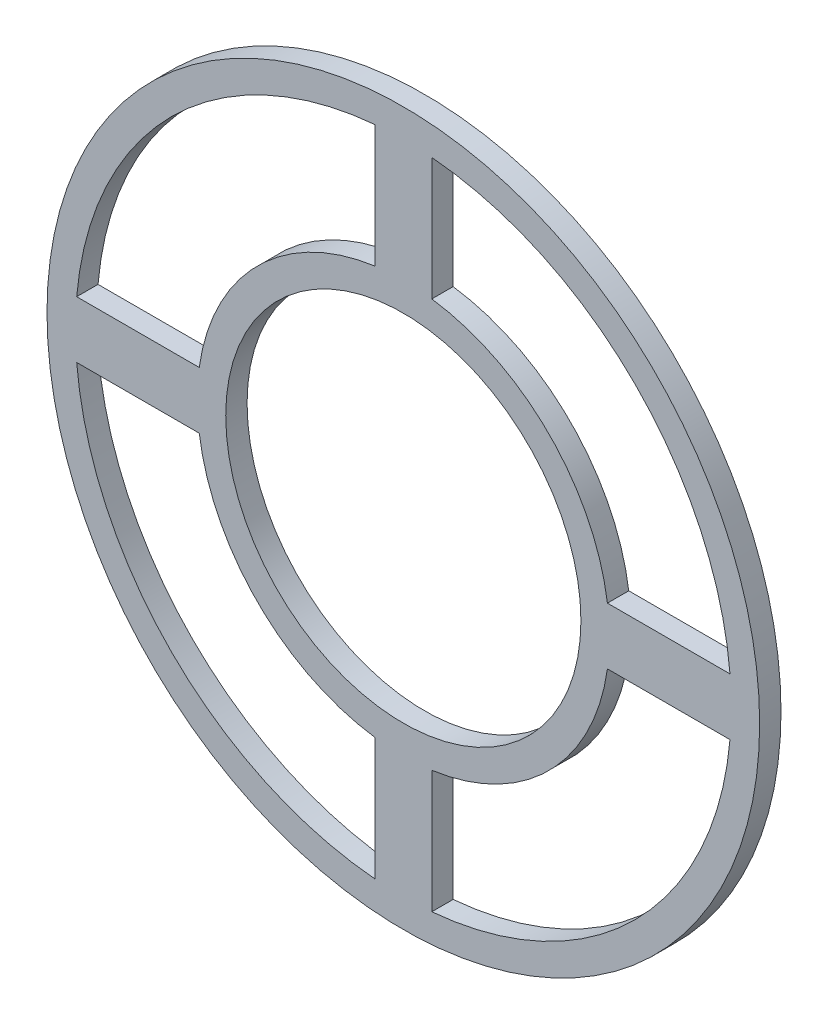
SolidWorks part; units mm, degrees
ref_plane "Front Plane" through (0, 0, 0) normal (0, 0, 1) x (1, 0, 0)
ref_plane "Top Plane" through (0, 0, 0) normal (0, 1, 0) x (1, 0, 0)
ref_plane "Right Plane" through (0, 0, 0) normal (1, 0, 0) x (0, 0, -1)
sketch "Sketch1" plane through (0, 0, 0) normal (0, 0, 1) x (1, 0, 0)
  line L0 (-6.35, 45.5334) -> (-6.35, 72.8759)
  line L1 (6.35, 45.5334) -> (6.35, 72.8759)
  line L3 (-45.5334, 6.35) -> (-72.8759, 6.35)
  line L4 (-45.5334, -6.35) -> (-72.8759, -6.35)
  line L5 (-6.35, -45.5334) -> (-6.35, -72.8759)
  line L6 (6.35, -45.5334) -> (6.35, -72.8759)
  line L7 (45.5334, 6.35) -> (72.8759, 6.35)
  line L8 (45.5334, -6.35) -> (72.8759, -6.35)
  circle A0 centre (0, 0) radius 39.624
  circle A1 centre (0, 0) radius 79.502
  arc A2 (-6.35, 72.8759) -> (-72.8759, 6.35) centre (0, 0) ccw
  arc A3 (-6.35, 45.5334) -> (-45.5334, 6.35) centre (0, 0) ccw
  arc A4 (-45.5334, -6.35) -> (-6.35, -45.5334) centre (0, 0) ccw
  arc A5 (6.35, -45.5334) -> (45.5334, -6.35) centre (0, 0) ccw
  arc A6 (6.35, -72.8759) -> (6.35, 72.8759) centre (0, 0) ccw
  arc A7 (45.5334, 6.35) -> (6.35, 45.5334) centre (0, 0) ccw
  arc A8 (-72.8759, -6.35) -> (-6.35, -72.8759) centre (0, 0) ccw
  point P9 (0, 0)
  dimension "D1" = 79.248
  dimension "D2" = 159.004
  dimension "D4" = 6.35
  dimension "D5" = 6.35
  dimension "D3" = 12.7
extrude "Boss-Extrude1" add sketch "Sketch1" along normal blind 4.7625 contours A1 A8 L4 A4 L5 A0 L0 A3 L3 A2 L7 A7 L1 A6 L6 A5 L8 region at (-77.2533, 0, 0)
